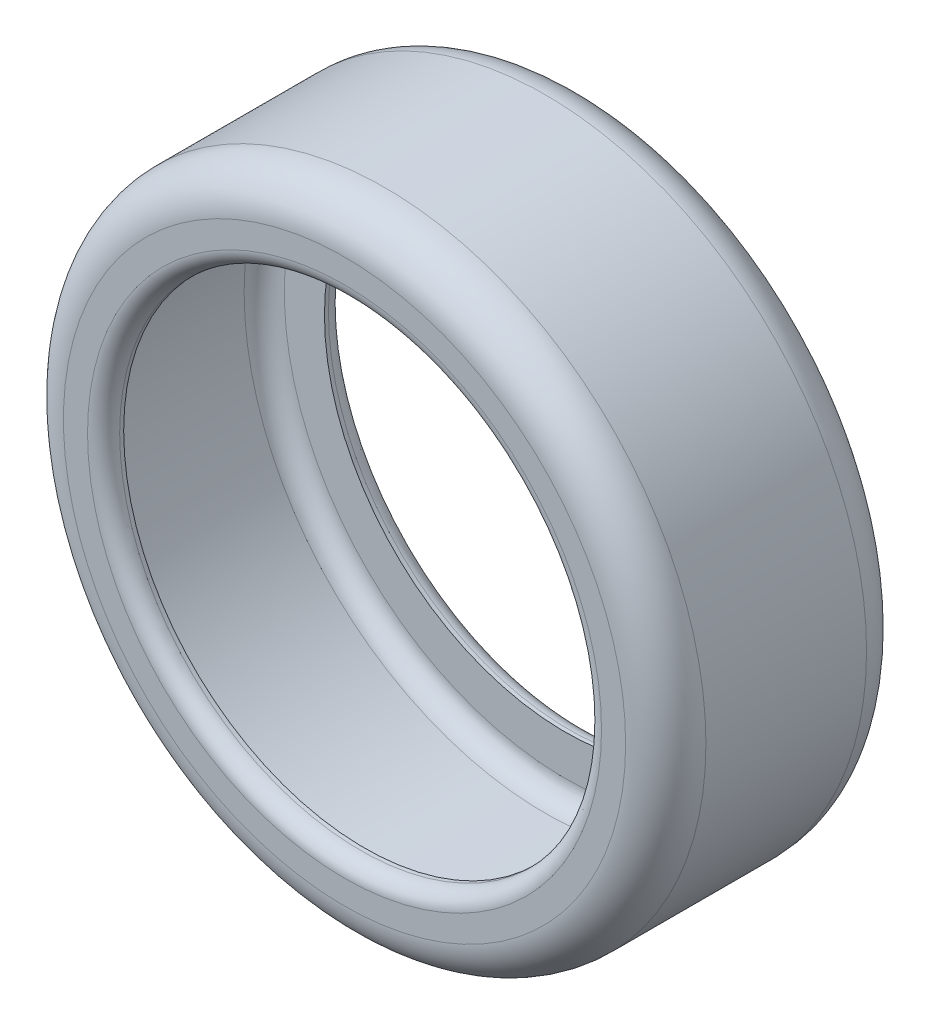
SolidWorks part; units mm, degrees
material "BUTYL"
ref_plane "Front Plane" through (0, 0, 0) normal (0, 0, 1) x (1, 0, 0)
ref_plane "Top Plane" through (0, 0, 0) normal (0, 1, 0) x (1, 0, 0)
ref_plane "Right Plane" through (0, 0, 0) normal (1, 0, 0) x (0, 0, -1)
sketch "Sketch3" plane through (0, 0, 0) normal (0, 0, 1) x (1, 0, 0)
  circle A0 centre (0, 0) radius 101.6
  circle A1 centre (0, 0) radius 76.2
  dimension "D1" = 203.2
  dimension "D2" = 152.4
extrude "Boss-Extrude1" add sketch "Sketch3" along normal blind 76.2
fillet "Fillet1" radius 12.7 2 edges at (101.6, 0, 0) (101.6, 0, 76.2)
fillet "Fillet2" radius 5.08 2 edges at (76.2, 0, 0) (76.2, 0, 76.2)
shell "Shell1" thickness 6.35 removed face at (76.2, 0, 5.08)
